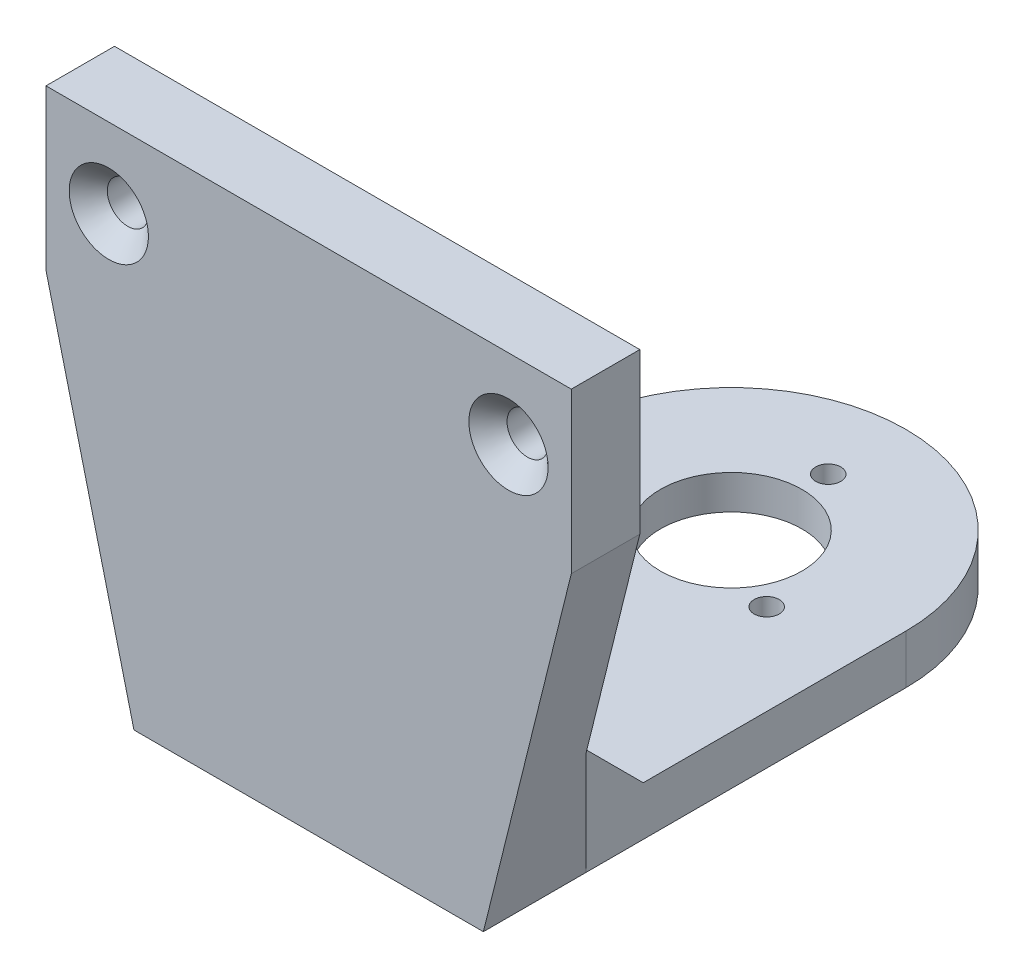
SolidWorks part; units mm, degrees
ref_plane "Płaszczyzna przednia" through (0, 0, 0) normal (0, 0, 1) x (1, 0, 0)
ref_plane "Płaszczyzna górna" through (0, 0, 0) normal (0, 1, 0) x (1, 0, 0)
ref_plane "Płaszczyzna prawa" through (0, 0, 0) normal (1, 0, 0) x (0, 0, -1)
sketch "Sketch1" plane through (0, 0, 0) normal (0, 1, 0) x (1, 0, 0)
  circle A0 centre (0, 0) radius 13.3
  circle A1 centre (0, 0) radius 6.2
  dimension "D1" = 26.6
  dimension "D2" = 12.4
extrude "Boss-Extrude1" add sketch "Sketch1" along normal blind 3
hole_wizard "M2 Clearance Hole1" positions "Sketch2" profile "Sketch4" hole size "M2" standard "DIN" end condition through all
sketch "Sketch2" plane through (0, 3, 0) normal (0, 1, 0) x (1, 0, 0)
  circle A0 centre (0, 0) radius 8.5 construction
  point P4 (0, 8.5)
  point P10 (7.3612, -4.25)
  point P11 (-7.3612, -4.25)
  dimension "D1" = 17
  dimension "D2" = 3
sketch "Sketch4" plane through (-7.3612, 3, 4.25) normal (1, 0, 0) x (0, 0, 1)
  line L0 (0, 0) -> (0, 3)
  line L1 (0, 3) -> (1.1, 3)
  line L2 (1.1, 3) -> (1.1, 0)
  line L5 (1.1, 0) -> (0, 0)
  line L11 (0, -6.35) -> (0, 107.95) construction
  dimension "Thru Hole Dia." = 2.2
  dimension "Thru Hole Depth" = 3
sketch "Sketch5" plane through (0, 3, 0) normal (0, 1, 0) x (1, 0, 0)
  circle A0 centre (0, 0) radius 13.3 construction
  circle A1 centre (0, 0) radius 13.3
  circle A2 centre (0, 0) radius 15.3
  dimension "D1" = 2
extrude "Boss-Extrude2" add sketch "Sketch5" against normal blind 4.3
sketch "Sketch6" plane through (0, 3, 0) normal (0, 1, 0) x (1, 0, 0)
  line L0 (-15.3, 0) -> (-15.3, -31)
  line L1 (-15.3, -31) -> (15.3, -31)
  line L2 (15.3, -31) -> (15.3, 0)
  circle A0 centre (0, 0) radius 15.3 construction
  arc A1 (-15.3, 0) -> (15.3, 0) centre (0, 0) ccw
  dimension "D1" = 31
extrude "Boss-Extrude3" add sketch "Sketch6" against normal up to surface (4.3 mm away) up to face at (0, -1.3, 13.3)
sketch "Sketch7" plane through (0, 0, 31) normal (0, 0, 1) x (1, 0, 0)
  line L7 (15.3, -1.3) -> (15.3, 3) construction
  line L8 (-15.3, -1.3) -> (15.3, -1.3)
  line L9 (-15.3, -1.3) -> (-15.3, 43.7)
  line L10 (-15.3, 43.7) -> (15.3, 43.7)
  line L11 (15.3, -1.3) -> (15.3, 43.7)
  dimension "D1" = 45
extrude "Boss-Extrude4" add sketch "Sketch7" along normal blind 6
sketch "Sketch8" plane through (0, 0, 37) normal (0, 0, 1) x (1, 0, 0)
  line L1 (-23, 43.7) -> (23, 43.7)
  line L2 (-23, 43.7) -> (-23, 29.7)
  line L3 (-23, 29.7) -> (23, 29.7)
  line L4 (23, 43.7) -> (23, 29.7)
  line L6 (15.3, 43.7) -> (-15.3, 43.7) construction
  line L7 (23, 31.3811) -> (15.3, 31.3811) construction
  line L8 (15.3, -1.3) -> (15.3, 43.7) construction
  line L10 (-15.3, 43.7) -> (-15.3, -1.3) construction
  line L11 (-15.3, 40.157) -> (-23, 40.157) construction
  dimension "D1" = 46
  dimension "D3" = 14
extrude "Boss-Extrude5" add sketch "Sketch8" against normal up to surface (6 mm away) up to face at (0, 23.35, 31)
sketch "Sketch9" plane through (0, 0, 37) normal (0, 0, 1) x (1, 0, 0)
  line L0 (-23, 29.7) -> (-15.3, -1.3)
  line L1 (15.3, -1.3) -> (23, 29.7)
  line L2 (-15.3, 29.7) -> (-15.3, -1.3) construction
  line L3 (-23, 29.7) -> (-15.3, 29.7) construction
  line L4 (15.3, -1.3) -> (15.3, 29.7) construction
  line L5 (15.3, 29.7) -> (23, 29.7) construction
  line L6 (-15.3, 29.7) -> (-15.3, -1.3)
  line L7 (-23, 29.7) -> (-15.3, 29.7)
  line L8 (15.3, -1.3) -> (15.3, 29.7)
  line L9 (15.3, 29.7) -> (23, 29.7)
extrude "Boss-Extrude6" add sketch "Sketch9" against normal up to surface (6 mm away) up to face at (0, 26.525, 31)
chamfer "Chamfer1" distance 8 angle 45 1 edges at (0, 3, 31)
chamfer "Chamfer2" distance 3 angle 45 2 edges at (15.3, 4.85, 31) (-15.3, 4.85, 31)
hole_wizard "CSK for M3 Hex Socket Countersunk Head Screw1" positions "Sketch10" profile "Sketch11" countersink size "M3" standard "DIN" end condition through all
sketch "Sketch10" plane through (0, 0, 37) normal (0, 0, 1) x (1, 0, 0)
  circle A0 centre (17.5, 36.7528) radius 2.1 construction
  circle A1 centre (-17.5, 36.7528) radius 2.1 construction
  point P0 (17.5, 36.7528)
  point P2 (-17.5, 36.7528)
sketch "Sketch11" plane through (17.5, 36.7528, 37) normal (1, 0, 0) x (0, -1, 0)
  line L0 (0, 0) -> (0, 52.3)
  line L1 (0, 52.3) -> (1.8, 52.3)
  line L2 (1.8, 52.3) -> (1.8, 1.67)
  line L3 (1.8, 1.67) -> (3.47, 0)
  line L5 (3.47, 0) -> (0, 0)
  line L6 (-1.8, 1.67) -> (-3.47, 0) construction
  line L11 (0, -6.35) -> (0, 107.95) construction
  dimension "Thru Hole Dia." = 3.6
  dimension "Thru Hole Depth" = 52.3
  dimension "Near C'Sink Dia." = 6.94
  dimension "Near C'Sink Angle" = 90
